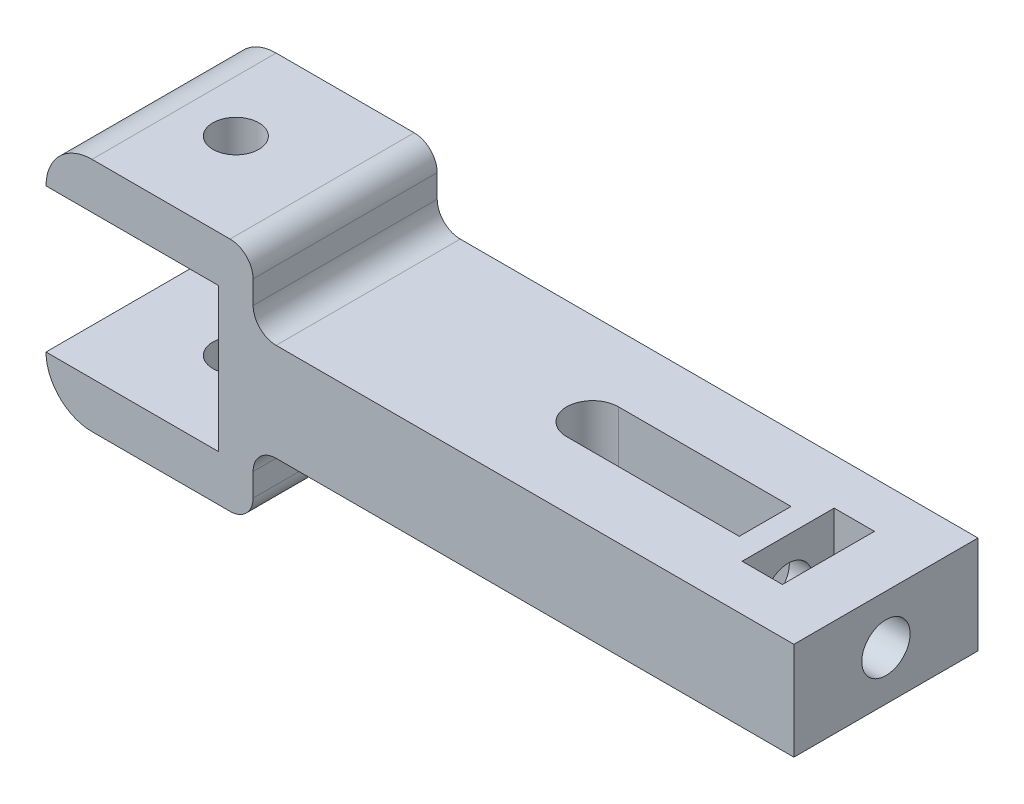
SolidWorks part; units mm, degrees
ref_plane "Front Plane" through (0, 0, 0) normal (0, 0, 1) x (1, 0, 0)
ref_plane "Top Plane" through (0, 0, 0) normal (0, 1, 0) x (1, 0, 0)
ref_plane "Right Plane" through (0, 0, 0) normal (1, 0, 0) x (0, 0, -1)
sketch "Sketch1" plane through (0, 0, 0) normal (0, 0, 1) x (1, 0, 0)
  line L0 (0, 0) -> (-47, 0)
  line L1 (-47, 0) -> (-47, 6)
  line L2 (-47, 6) -> (-65, 6)
  line L3 (-65, 6) -> (-65, 2)
  line L4 (-65, 2) -> (-50, 2)
  line L5 (-50, 2) -> (-50, -10.5)
  line L6 (0, 0) -> (0, -8.5)
  line L7 (0, -4.25) -> (-50, -4.25) construction
  line L8 (-65, -10.5) -> (-50, -10.5)
  line L9 (-65, -14.5) -> (-65, -10.5)
  line L10 (-47, -14.5) -> (-65, -14.5)
  line L11 (-47, -8.5) -> (-47, -14.5)
  line L12 (0, -8.5) -> (-47, -8.5)
  dimension "D1" = 65
  dimension "D2" = 15
  dimension "D3" = 4.25
  dimension "D4" = 6.25
  dimension "D5" = 4
  dimension "D6" = 18
extrude "Boss-Extrude1" add sketch "Sketch1" along normal blind 16
sketch "Sketch2" plane through (0, 0, 0) normal (0, 1, 0) x (1, 0, 0)
  line L0 (0, -8) -> (-47, -8) construction
  line L1 (0, -16) -> (0, 0) construction
  line L2 (-47, -16) -> (-47, 0) construction
  line L4 (-8.5, -4) -> (-5, -4)
  line L5 (-8.5, -4) -> (-8.5, -12)
  line L6 (-8.5, -12) -> (-5, -12)
  line L7 (-5, -4) -> (-5, -12)
  line L8 (-8.5, -4) -> (-5, -12) construction
  line L9 (-8.5, -12) -> (-5, -4) construction
  line L10 (-25.5, -10.25) -> (-10.5, -10.25)
  line L12 (-25.5, -5.75) -> (-10.5, -5.75)
  line L13 (-10.5, -10.25) -> (-10.5, -5.75)
  line L14 (-25.5, -10.25) -> (-10.5, -5.75) construction
  line L15 (-25.5, -5.75) -> (-10.5, -10.25) construction
  arc A0 (-25.5, -5.75) -> (-25.5, -10.25) centre (-25.5, -8) ccw
  point P6 (-6.75, -8)
  point P11 (-18, -8)
  dimension "D7" = 2.25
  dimension "D1" = 8
  dimension "D2" = 3.5
  dimension "D3" = 5
  dimension "D4" = 2
  dimension "D5" = 4.5
  dimension "D6" = 15
extrude "Cut-Extrude1" cut sketch "Sketch2" against normal through all
sketch "Sketch3" plane through (0, 0, 0) normal (1, 0, 0) x (0, 0, -1)
  line L0 (-8, 0) -> (-8, -8.5) construction
  line L1 (-16, 0) -> (0, 0) construction
  line L2 (-16, -8.5) -> (0, -8.5) construction
  circle A0 centre (-8, -4.25) radius 2.1
  dimension "D1" = 4.2
extrude "Cut-Extrude2" cut sketch "Sketch3" against normal up to surface (10.5 mm away) up to face at (-10.5, -4.25, 8)
fillet "Fillet1" radius 2 4 edges at (-47, -8.5, 8) (-47, 6, 8) (-47, 0, 8) (-47, -14.5, 8)
sketch "Sketch4" plane through (0, -10.5, 0) normal (0, 1, 0) x (1, 0, 0)
  line L0 (-65, -8) -> (-49, -8) construction
  line L1 (-65, -16) -> (-65, 0) construction
  line L2 (-49, 0) -> (-49, -16) construction
  circle A0 centre (-57, -8) radius 9
  dimension "D1" = 18
extrude "Cut-Extrude3" cut sketch "Sketch4" along normal up to surface (12.5 mm away) up to face at (-57.5, 2, 8)
sketch "Sketch5" plane through (0, 6, 0) normal (0, 1, 0) x (1, 0, 0)
  line L0 (-65, -8) -> (-49, -8) construction
  line L1 (-65, -16) -> (-65, 0) construction
  line L2 (-49, -16) -> (-49, 0) construction
  circle A0 centre (-56.5, -8) radius 2
  dimension "D1" = 4
  dimension "D2" = 8.5
extrude "Cut-Extrude4" cut sketch "Sketch5" against normal through all
fillet "Fillet2" radius 4 2 edges at (-65, -14.5, 8) (-65, 6, 8)
equation "\"X-ROD-SPACING\"=45"
equation "\"Y-ROD-SPACING\"=75"
equation "\"Z-ROD-SPACING\"=17.5"
equation "\"Y-BED-OFFSET\"=2"
equation "\"Y-BED-ROD-INSET\"=3.5"
equation "\"T-SLOT-NUT-FILLET-RADIUS\"=0.25"
equation "\"T-SLOT-SCREW-SHAFT-RADIUS\"=1.75"
equation "\"T-SLOT-SCREW-SHAFT-CUTOUT-LENGTH\"=10.5"
equation "\"T-SLOT-NUT-DEPTH\"=4.2"
equation "\"T-SLOT-NUT-WIDTH\"=3"
equation "\"T-SLOT-NUT-END-DISTANCE\"=8"
equation "\"ACRYLIC-THICKNESS\"=10"
equation "\"ACRYLIC-TAB-CUTOUT-SIZE\"=\"ACRYLIC-THICKNESS\"+\"ACRYLIC-TAB-TOLERANCE\"*2"
equation "\"ACRYLIC-TAB-WIDTH\"=\"ACRYLIC-THICKNESS\""
equation "\"ACRYLIC-M3-HOLE\"=3.2"
equation "\"SMOOTHROD-CAP-SCREW-DISTANCE\"=20"
equation "\"FRAME-WIDTH-INNER\"=370"
equation "\"NEMA17-HOLE-SPACING\"=31"
equation "\"NEMA17-CENTRAL-CUTOUT\"=22.5"
equation "\"Z-BRACKET-REACH\"=55"
equation "\"TOP-BRACKET-SPACING\"=40"
equation "\"SMOOTHROD-X-LENGTH\"=350"
equation "\"SMOOTHROD-Y-LENGTH\"=350"
equation "\"SMOOTHROD-Z-LENGTH\"=350"
equation "\"SMOOTHROD-TIGHTENING-HEADROOM\"=1"
equation "\"LEADSCREW-Z-LENGTH\"=300"
equation "\"SCREW-HEAD-RADIUS\"=6"
equation "\"PRINTED-X-SMOOTHROD-DIAMETER\"=8.2"
equation "\"PRINTED-X-SMOOTHROD-CUTOUT\"=10"
equation "\"PRINTED-X-BASE-HEIGHT\"=10"
equation "\"PRINTED-LM8UU-CUTOUT-SIZE\"=15.25"
equation "\"PRINTED-LM8UU-CUTOUT-LENGTH\"=24.5"
equation "\"PRINTED-X-IDLER-HEIGHT\"=16"
equation "\"D1@Boss-Extrude1\"=\"PRINTED-X-IDLER-HEIGHT\""
